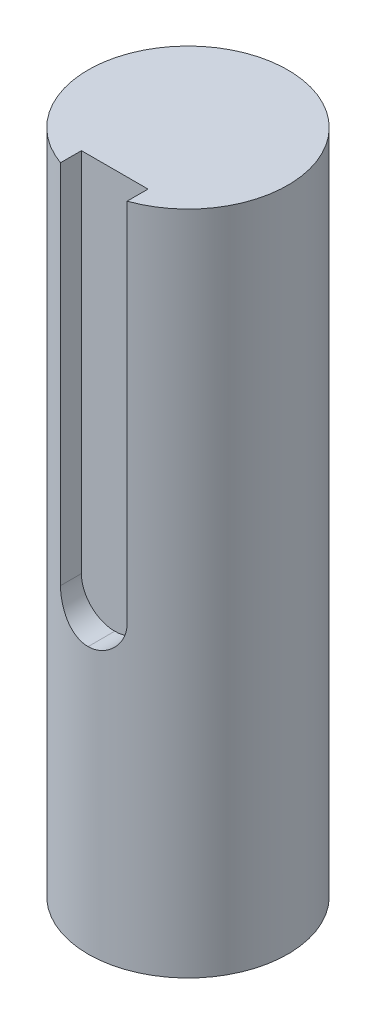
SolidWorks part; units mm, degrees
ref_plane "Front Plane" through (0, 0, 0) normal (1, 0, 0) x (0, 1, 0)
ref_plane "Top Plane" through (0, 0, 0) normal (0, 0, 1) x (0, 1, 0)
ref_plane "Right Plane" through (0, 0, 0) normal (0, 1, 0) x (-1, 0, 0)
sketch "Sketch2" plane through (0, 0, 0) normal (0, 1, 0) x (-1, 0, 0)
  circle A0 centre (0, 0) radius 15
  dimension "D1" = 30
extrude "Boss-Extrude1" add sketch "Sketch2" along normal mid plane 100
sketch "Sketch3" plane through (0, 50, 0) normal (0, 1, 0) x (-1, 0, 0)
  line L1 (-5, 19) -> (5, 19)
  line L2 (-5, 19) -> (-5, 11)
  line L3 (-5, 11) -> (5, 11)
  line L4 (5, 19) -> (5, 11)
  line L5 (-5, 19) -> (5, 11) construction
  line L6 (-5, 11) -> (5, 19) construction
  circle A0 centre (0, 0) radius 15 construction
  point P0 (0, 15)
  dimension "D1" = 10
  dimension "D2" = 8
extrude "Cut-Extrude1" cut sketch "Sketch3" against normal blind 60
fillet "Fillet1" radius 5 2 edges at (5, -10, 12.5711) (-5, -10, 12.5711)
ref_axis "Axis1" through (0, 50, 0) along (0, -1, 0)
